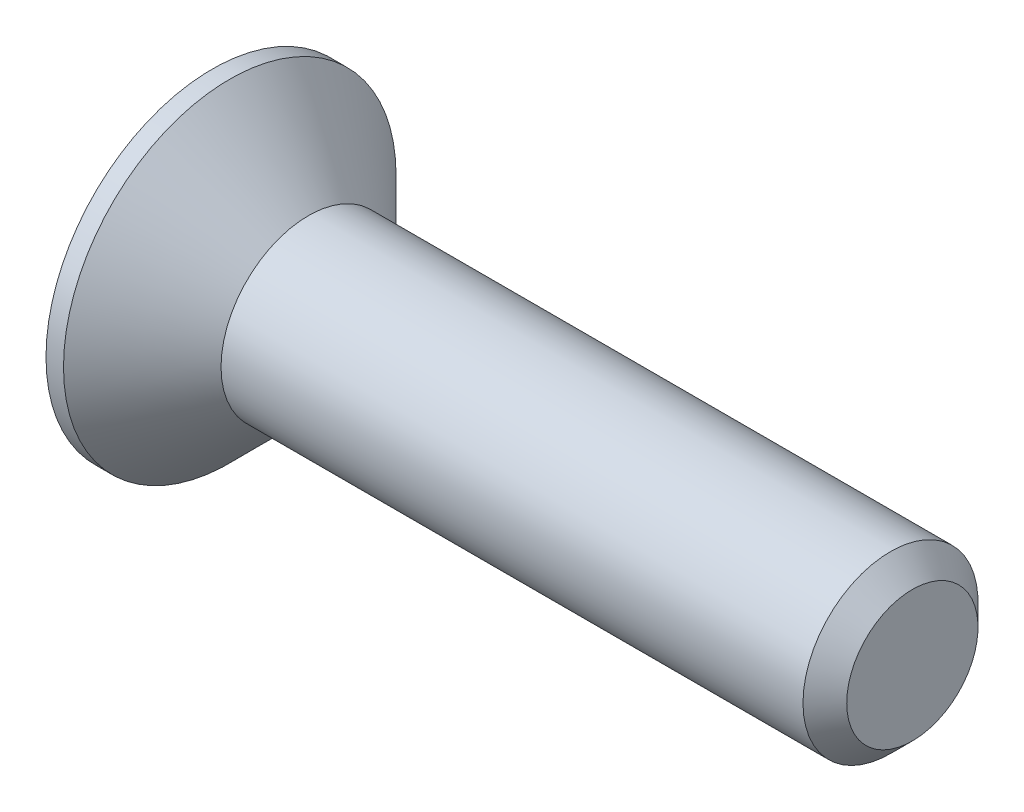
SolidWorks part; units mm, degrees
ref_plane "Front Plane" through (0, 0, 0) normal (0, 0, 1) x (1, 0, 0)
ref_plane "Top Plane" through (0, 0, 0) normal (0, 1, 0) x (1, 0, 0)
ref_plane "Right Plane" through (0, 0, 0) normal (1, 0, 0) x (0, 0, -1)
sketch "Sketch2" plane through (0, 0, 0) normal (0, 0, 1) x (1, 0, 0)
  line L0 (0, 0) -> (0, 1.9)
  line L1 (0, 1.9) -> (0.2, 1.9)
  line L2 (0.2, 1.9) -> (1.1, 1)
  line L3 (1.1, 1) -> (7.75, 1)
  line L4 (7.75, 1) -> (8, 0.75)
  line L5 (8, 0.75) -> (8, 0)
  line L6 (8, 0) -> (0, 0)
  line L7 (-2.2818, 0) -> (8.0811, 0) construction
  dimension "D1" = 3.8
  dimension "D2" = 0.2
  dimension "D3" = 45
  dimension "D4" = 8
  dimension "D5" = 0.25
  dimension "D6" = 2
revolve "Revolve1" add sketch "Sketch2" angle 360 about L7
sketch "Sketch3" plane through (0, 0, 0) normal (-1, 0, 0) x (0, 0, 1)
  line L1 (0.433, -0.75) -> (0.866, 0)
  line L2 (0.866, 0) -> (0.433, 0.75)
  line L3 (0.433, 0.75) -> (-0.433, 0.75)
  line L4 (-0.433, 0.75) -> (-0.866, 0)
  line L5 (-0.866, 0) -> (-0.433, -0.75)
  line L6 (-0.433, -0.75) -> (0.433, -0.75)
  circle A0 centre (0, 0) radius 0.75 construction
  dimension "D1" = 1.5
extrude "Cut-Extrude1" cut sketch "Sketch3" against normal blind 0.8
